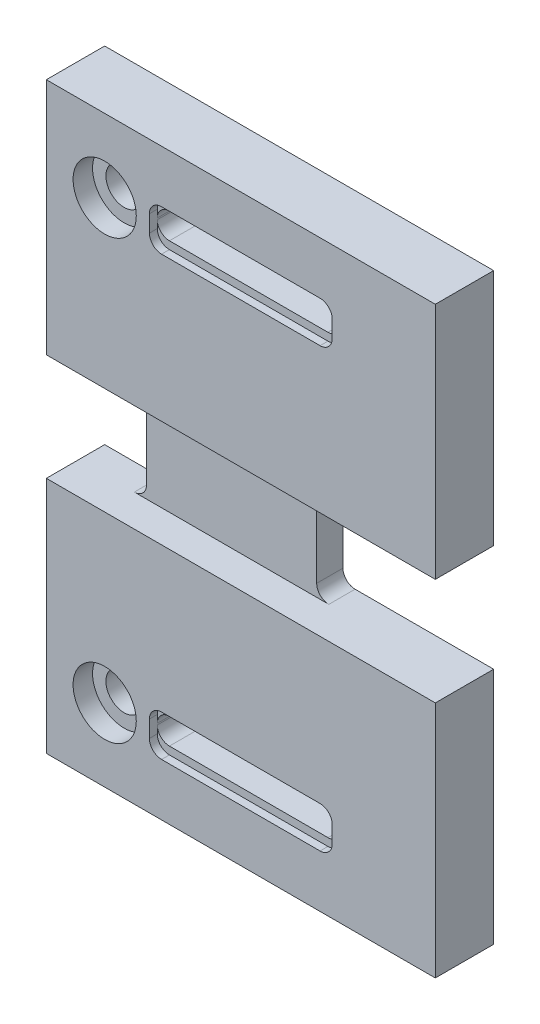
SolidWorks part; units mm, degrees
ref_plane "Front Plane" through (0, 0, 0) normal (1, 0, 0) x (0, 1, 0)
ref_plane "Top Plane" through (0, 0, 0) normal (0, 0, 1) x (0, 1, 0)
ref_plane "Right Plane" through (0, 0, 0) normal (0, 1, 0) x (-1, 0, 0)
sketch "Sketch1" plane through (0, 0, 0) normal (0, 0, 1) x (0, 1, 0)
  line L0 (-38.1, 25.4) -> (38.1, -25.4) construction
  line L1 (-38.1, 25.4) -> (38.1, 25.4)
  line L2 (-38.1, 25.4) -> (-38.1, -25.4)
  line L3 (-38.1, -25.4) -> (38.1, -25.4)
  line L4 (38.1, 25.4) -> (38.1, -25.4)
  line L5 (38.1, 25.4) -> (-38.1, -25.4) construction
  dimension "D1" = 50.8
  dimension "D2" = 76.2
extrude "Boss-Extrude1" add sketch "Sketch1" along normal blind 7.62 contours L2 L3 L4 L1
sketch "Sketch2" plane through (0, 0, 7.62) normal (0, 0, 1) x (1, 0, 0)
  line L0 (-25.4, 6.985) -> (25.4, 6.985)
  line L1 (-25.4, -38.1) -> (-25.4, 38.1) construction
  line L2 (25.4, -38.1) -> (25.4, 38.1) construction
  line L3 (25.4, 6.985) -> (25.4, -6.985)
  line L4 (25.4, -6.985) -> (-25.4, -6.985)
  line L5 (-25.4, -6.985) -> (-25.4, 6.985)
  line L6 (-25.4, 0) -> (25.4, 0) construction
  dimension "D1" = 13.97
extrude "Cut-Extrude1" cut sketch "Sketch2" against normal offset from surface (4.191 mm away) 3.429 up to face at (0, 0, 0)
sketch "Sketch3" plane through (0, 0, 0) normal (0, 0, -1) x (1, 0, 0)
  line L0 (-25.4, 6.985) -> (-16.51, 6.985)
  line L1 (-25.4, 38.1) -> (-25.4, -38.1) construction
  line L2 (-16.51, 6.985) -> (-16.51, -6.985)
  line L3 (-16.51, -6.985) -> (-25.4, -6.985)
  line L4 (-25.4, -6.985) -> (-25.4, 6.985)
  line L5 (25.4, 6.985) -> (5.715, 6.985)
  line L6 (25.4, 38.1) -> (25.4, -38.1) construction
  line L7 (5.715, 6.985) -> (5.715, -6.985)
  line L8 (5.715, -6.985) -> (25.4, -6.985)
  line L9 (-16.51, 0) -> (5.715, 0) construction
  line L10 (25.4, 6.985) -> (25.4, -6.985)
  dimension "D1" = 13.97
  dimension "D2" = 8.89
  dimension "D3" = 19.685
extrude "Cut-Extrude2" cut sketch "Sketch3" against normal through all
sketch "Sketch4" plane through (0, 0, 7.62) normal (0, 0, 1) x (1, 0, 0)
  line L0 (0, 0) -> (19.05, 0) construction
  line L1 (19.05, 28.575) -> (19.05, -28.575) construction
  line L2 (25.4, 6.985) -> (25.4, 38.1) construction
  line L3 (-17.78, 28.575) -> (-17.78, -28.575) construction
  line L4 (-17.78, 0) -> (0, 0) construction
  line L5 (-17.78, 28.575) -> (19.05, 28.575) construction
  circle A2 centre (-17.78, 28.575) radius 2.3813
  circle A3 centre (-17.78, -28.575) radius 2.3813
  dimension "D4" = 4.7625
  dimension "D3" = 6.35
  dimension "D5" = 57.15
  dimension "D6" = 17.78
extrude "Cut-Extrude3" cut sketch "Sketch4" against normal through all contours A2 | A3
sketch "Sketch5" plane through (0, 0, 7.62) normal (0, 0, 1) x (1, 0, 0)
  line L0 (-11.938, 30.2578) -> (11.938, 30.2578)
  line L1 (11.938, 30.2578) -> (11.938, 26.8923)
  line L2 (11.938, 26.8923) -> (-11.938, 26.8923)
  line L3 (-11.938, 26.8923) -> (-11.938, 30.2578)
  line L4 (-11.938, 28.575) -> (-15.3987, 28.575) construction
  line L5 (0, 0) -> (0, 26.8923) construction
  line L10 (-1.27, 29.21) -> (-1.27, 30.2578) construction
  line L11 (11.684, 28.575) -> (11.938, 28.575) construction
  line L12 (7.62, 29.21) -> (-10.16, 29.21) construction
  line L13 (-11.938, 26.8923) -> (-11.938, -26.8923) construction
  line L14 (4.191, 0) -> (-4.191, 0) construction
  line L15 (-11.938, -26.8923) -> (-11.938, -30.2578)
  line L16 (-11.938, -30.2578) -> (11.938, -30.2578)
  line L17 (11.938, -30.2578) -> (11.938, -26.8923)
  line L18 (11.938, -26.8923) -> (-11.938, -26.8923)
  circle A0 centre (-17.78, 28.575) radius 2.3813 construction
  dimension "D1" = 3.3655
  dimension "D2" = 23.876
  dimension "D3" = 0.254
extrude "Cut-Extrude4" cut sketch "Sketch5" against normal through all contours L1 L2 L3 L0 | L15 L16 L17 L18
sketch "Sketch6" plane through (0, 0, 7.62) normal (0, 0, 1) x (1, 0, 0)
  line L0 (-11.938, 25.8922) -> (-11.938, 26.8923)
  line L1 (-11.938, 26.8923) -> (11.938, 26.8923)
  line L2 (11.938, 26.8923) -> (11.938, 25.8922)
  line L3 (-11.938, 25.8922) -> (11.938, 25.8922)
  line L4 (4.191, 0) -> (-4.191, 0) construction
  line L5 (11.938, -26.8923) -> (11.938, -25.8922)
  line L6 (-11.938, -25.8922) -> (-11.938, -26.8923)
  line L7 (-11.938, -26.8923) -> (11.938, -26.8923)
  line L8 (-11.938, -25.8922) -> (11.938, -25.8922)
  line L9 (-11.938, 30.2578) -> (11.938, 30.2578)
  line L10 (11.938, 30.2578) -> (11.938, 31.2578)
  line L11 (11.938, 31.2578) -> (-11.938, 31.2578)
  line L12 (-11.938, 31.2578) -> (-11.938, 30.2578)
  line L13 (11.938, -30.2578) -> (11.938, -31.2578)
  line L14 (-11.938, -30.2578) -> (11.938, -30.2578)
  line L15 (-11.938, -31.2578) -> (-11.938, -30.2578)
  line L16 (11.938, -31.2578) -> (-11.938, -31.2578)
  dimension "D1" = 1
extrude "Cut-Extrude5" cut sketch "Sketch6" against normal blind 1.0254
fillet "Fillet3" radius 1.5875 4 edges at (-16.51, -6.985, 1.7145) (-16.51, 6.985, 1.7145) (5.715, -6.985, 1.7145) (5.715, 6.985, 1.7145)
fillet "Fillet6" radius 1.5875 8 edges at (11.938, 26.8923, 3.2973) (-11.938, 26.8923, 3.2973) (-11.938, 30.2578, 3.2973) (11.938, 30.2578, 3.2973) (-11.938, -26.8923, 3.2973) (-11.938, -30.2578, 3.2973) (11.938, -30.2578, 3.2973) (11.938, -26.8923, 3.2973)
fillet "Fillet7" radius 1.5875 8 edges at (-11.938, 25.8922, 7.1073) (11.938, 25.8922, 7.1073) (-11.938, -25.8922, 7.1073) (11.938, -25.8922, 7.1073) (11.938, 31.2578, 7.1073) (-11.938, 31.2578, 7.1073) (-11.938, -31.2578, 7.1073) (11.938, -31.2578, 7.1073)
sketch "Sketch7" plane through (0, 0, 7.62) normal (0, 0, 1) x (1, 0, 0)
  circle A1 centre (-17.78, -28.575) radius 4.1275
  circle A2 centre (-17.78, 28.575) radius 4.1275
  dimension "D1" = 8.255
extrude "Cut-Extrude6" cut sketch "Sketch7" against normal blind 2.54
